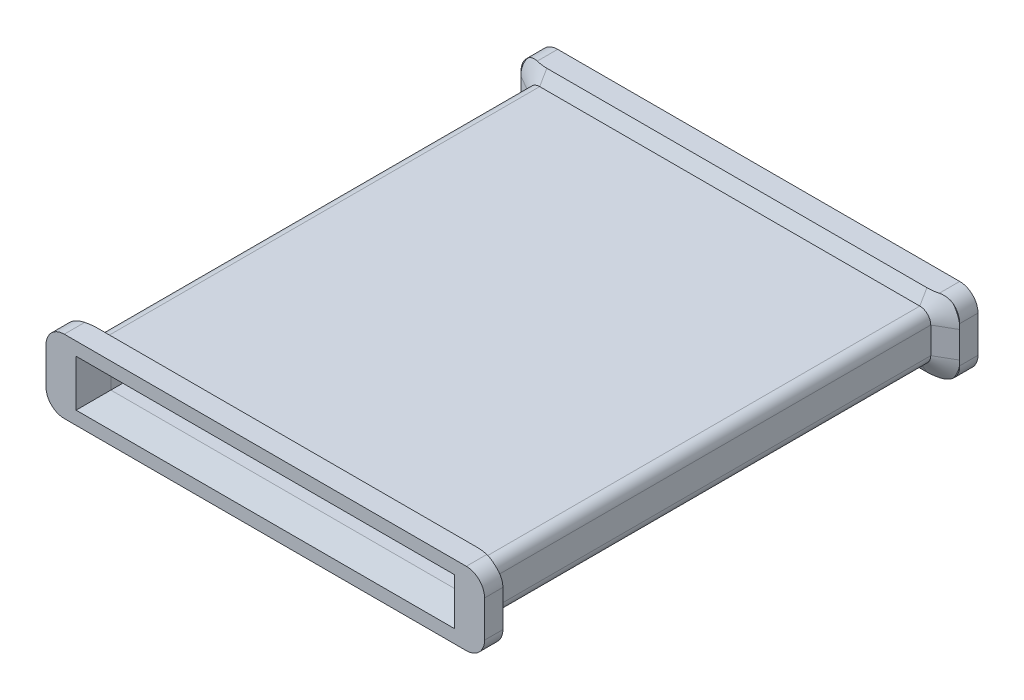
SolidWorks part; units mm, degrees
material "ABS"
ref_plane "Front Plane" through (0, 0, 0) normal (0, 0, 1) x (1, 0, 0)
ref_plane "Top Plane" through (0, 0, 0) normal (0, 1, 0) x (1, 0, 0)
ref_plane "Right Plane" through (0, 0, 0) normal (1, 0, 0) x (0, 0, -1)
sketch "Sketch1" plane through (0, 0, 0) normal (0, 0, 1) x (1, 0, 0)
  line L0 (0, 8) -> (48, 8)
  line L3 (48, 8) -> (48, 0)
  line L4 (48, 0) -> (0, 0)
  line L5 (0, 0) -> (0, 8)
  line L9 (3.6, 6.25) -> (44.4, 6.25)
  line L10 (3.6, 6.25) -> (3.6, 1.75)
  line L11 (3.6, 1.75) -> (44.4, 1.75)
  line L12 (44.4, 6.25) -> (44.4, 1.75)
  dimension "D1" = 1.75
  dimension "D2" = 40.8
  dimension "D4" = 4.5
  dimension "D5" = 1.75
  dimension "D7" = 3.6
  dimension "D8" = 3.6
extrude "Boss-Extrude1" add sketch "Sketch1" along normal blind 54
sketch "Sketch2" plane through (0, 0, 54) normal (0, 0, 1) x (1, 0, 0)
  line L1 (3.2, 6.65) -> (44.8, 6.65)
  line L2 (2, 5.45) -> (2, 2.55)
  line L3 (3.2, 1.35) -> (44.8, 1.35)
  line L4 (46, 5.45) -> (46, 2.55)
  line L5 (3.6, 1.75) -> (44.4, 1.75) construction
  line L6 (44.4, 6.25) -> (3.6, 6.25) construction
  line L8 (3.6, 6.25) -> (3.6, 1.75) construction
  line L9 (44.4, 1.75) -> (44.4, 6.25) construction
  arc A0 (2, 2.55) -> (3.2, 1.35) centre (3.2, 2.55) ccw
  arc A1 (44.8, 1.35) -> (46, 2.55) centre (44.8, 2.55) ccw
  arc A2 (44.8, 6.65) -> (46, 5.45) centre (44.8, 5.45) cw
  arc A3 (3.2, 6.65) -> (2, 5.45) centre (3.2, 5.45) ccw
  dimension "D1" = 1.2
  dimension "D2" = 0.4
  dimension "D3" = 1.6
  dimension "D4" = 1.6
  dimension "D5" = 0.4
extrude "Cut-Extrude1" cut sketch "Sketch2" against normal offset from surface (50 mm away) 2 from offset 2 flip side to cut up to face at (24, 4, 0) offset against normal yes
fillet "Fillet1" radius 2 8 edges at (48, 8, 53) (48, 0, 53) (48, 0, 1) (48, 8, 1) (0, 0, 1) (0, 8, 1) (0, 0, 53) (0, 8, 53)
chamfer "Chamfer4" distance 1.17 angle 60 16 edges at (2, 4, 52) (2.3515, 1.7015, 52) (2.3515, 6.2985, 52) (24, 1.35, 52) (24, 6.65, 52) (45.6485, 1.7015, 52) (45.6485, 6.2985, 52) (46, 4, 52) (2, 4, 2) (2.3515, 1.7015, 2) (2.3515, 6.2985, 2) (24, 1.35, 2) (24, 6.65, 2) (45.6485, 1.7015, 2) (45.6485, 6.2985, 2) (46, 4, 2) first distance on face at (2, 4, 27) first distance on face at (2.4757, 1.8257, 27) first distance on face at (2.4757, 6.1743, 27) first distance on face at (24, 1.35, 27) first distance on face at (24, 6.65, 27) first distance on face at (45.5243, 1.8257, 27) first distance on face at (45.5243, 6.1743, 27) first distance on face at (46, 4, 27)
chamfer "Chamfer5" distance 3.5 angle 5 8 edges at (44.4, 4, 54) (24, 1.75, 54) (3.6, 4, 54) (24, 6.25, 54) (44.4, 4, 0) (24, 1.75, 0) (3.6, 4, 0) (24, 6.25, 0) first distance on face at (44.4, 4, 27) first distance on face at (24, 1.75, 27) first distance on face at (3.6, 4, 27) first distance on face at (24, 6.25, 27)
